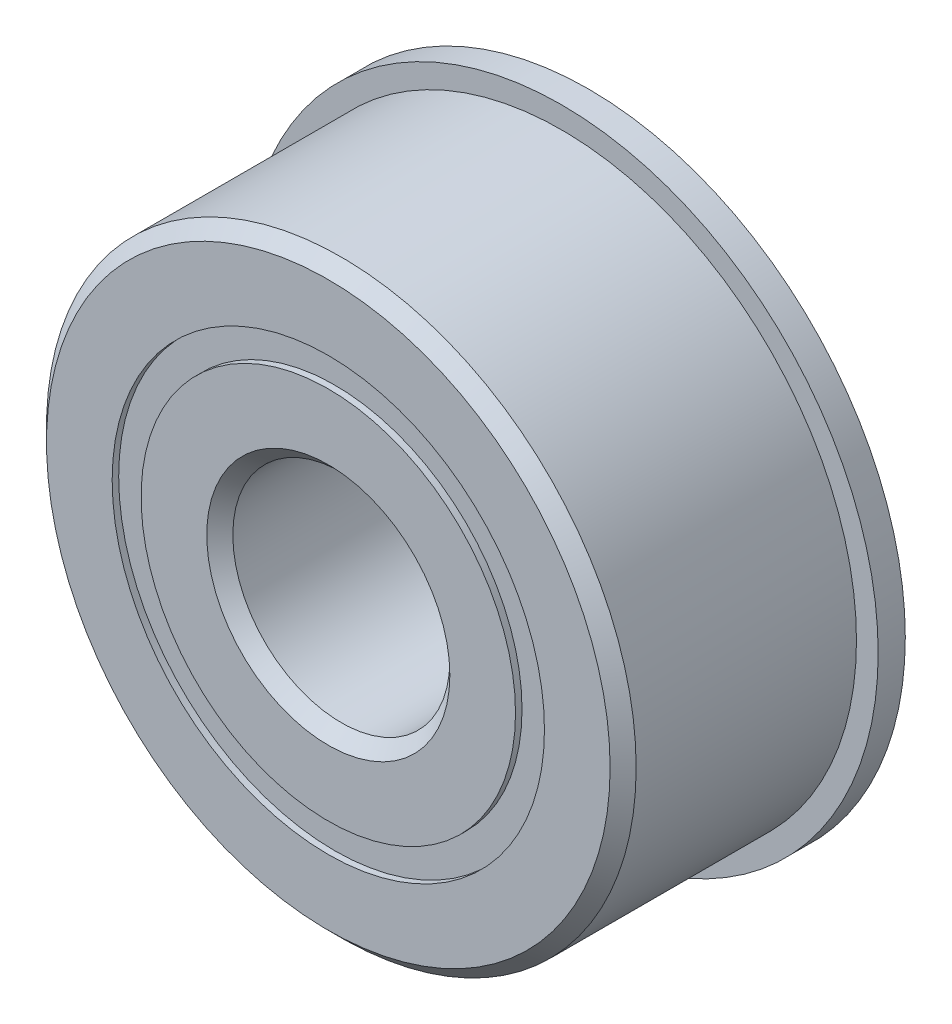
SolidWorks part; units mm, degrees
ref_plane "Front Plane" through (0, 0, 0) normal (0, 0, 1) x (1, 0, 0)
ref_plane "Top Plane" through (0, 0, 0) normal (0, 1, 0) x (1, 0, 0)
ref_plane "Right Plane" through (0, 0, 0) normal (1, 0, 0) x (0, 0, -1)
sketch "Sketch1" plane through (0, 0, 0) normal (1, 0, 0) x (0, 0, -1)
  line L0 (-3.6, 0) -> (3.6, 0) construction
  line L1 (0, 8.15) -> (0, -8.15) construction
  line L2 (3.24, 8.15) -> (-3.24, 8.15)
  line L3 (-3.24, 8.15) -> (-3.6, 7.79)
  line L4 (-3.6, 7.79) -> (-3.6, 5.975)
  line L5 (-3.6, 5.975) -> (-1.6, 5.975)
  line L6 (3.6, 5.975) -> (1.6, 5.975)
  line L7 (3.6, 7.79) -> (3.6, 5.975)
  line L8 (3.24, 8.15) -> (3.6, 7.79)
  line L9 (0, 8.15) -> (0, 5.575) construction
  line L10 (0, 5.575) -> (0, 3) construction
  arc A0 (-1.6, 5.975) -> (1.6, 5.975) centre (0, 5.575) cw
  point P14 (0, 3)
  dimension "Width" = 7.2
  dimension "OD" = 16.3
  dimension "D1" = 45
  dimension "D2" = 0.36
  dimension "Shaft Dia" = 6
  dimension "D3" = 3.2
  dimension "D4" = 0.4
revolve "Revolve1" add sketch "Sketch1" angle 360 about L0
sketch "Sketch3" plane through (0, 0, 0) normal (1, 0, 0) x (0, 0, -1)
  line L0 (-3.6, 5.175) -> (-1.6, 5.175)
  line L1 (0, 8.15) -> (0, -8.15) construction
  line L2 (-3.6, 7.79) -> (-3.6, 5.975) construction
  line L3 (-3.6, 5.175) -> (-3.6, 3.36)
  line L4 (-3.24, 8.15) -> (-3.6, 7.79) construction
  line L5 (-3.6, 3.36) -> (-3.24, 3)
  line L6 (-3.24, 3) -> (3.24, 3)
  line L7 (3.24, 8.15) -> (3.24, -8.15) construction
  line L8 (3.24, 3) -> (3.6, 3.36)
  line L9 (3.6, -7.79) -> (3.6, 7.79) construction
  line L10 (3.6, 3.36) -> (3.6, 5.175)
  line L11 (3.6, 5.175) -> (1.6, 5.175)
  line L13 (3.24, 8.15) -> (3.6, 7.79) construction
  arc A0 (1.6, 5.975) -> (-1.6, 5.975) centre (0, 5.575) ccw construction
  arc A1 (1.6, 5.175) -> (-1.6, 5.175) centre (0, 5.575) cw
revolve "Revolve3" add sketch "Sketch3" angle 360 about L0
sketch "Sketch4" plane through (0, 0, 0) normal (1, 0, 0) x (0, 0, -1)
  line L0 (-1.6492, 5.575) -> (1.6492, 5.575)
  arc A2 (-1.6492, 5.575) -> (1.6492, 5.575) centre (0, 5.575) cw
  arc A3 (1.6, 5.975) -> (-1.6, 5.975) centre (0, 5.575) ccw construction
revolve "Revolve4" add sketch "Sketch4" angle 360 about L0
ref_axis "Axis1" through (0, 0, -3.6) along (0, 0, 1)
pattern_circular "CirPattern1" count 8 every 45 about axis through (0, 0, -3.6) along (0, 0, 1) of bodies 104
sketch "Sketch5" plane through (0, 0, 0) normal (1, 0, 0) x (0, 0, -1)
  line L0 (-3.6, 5.975) -> (-1.6, 5.975) construction
  line L1 (-3.42, 5.975) -> (-1.6492, 5.975)
  line L2 (-3.42, 5.975) -> (-3.42, 5.175)
  line L3 (-3.42, 5.175) -> (-1.6492, 5.175)
  line L4 (-1.6492, 5.975) -> (-1.6492, 5.175)
  line L5 (-3.6, 5.175) -> (-1.6, 5.175) construction
  line L6 (3.6, 5.975) -> (1.6, 5.975) construction
  line L7 (3.42, 5.975) -> (1.6492, 5.975)
  line L8 (3.42, 5.975) -> (3.42, 5.175)
  line L9 (3.42, 5.175) -> (1.6492, 5.175)
  line L10 (1.6492, 5.975) -> (1.6492, 5.175)
  line L11 (3.6, 5.175) -> (1.6, 5.175) construction
  line L12 (-3.24, 8.15) -> (-3.6, 7.79) construction
  point P18 (-3.42, 7.97)
revolve "Revolve5" add sketch "Sketch5" angle 360 about L0
sketch "Sketch6" plane through (0, 0, 0) normal (1, 0, 0) x (0, 0, -1)
  line L0 (3.6, 0) -> (-3.6, 0) construction
  line L1 (3.6, 5.975) -> (2.85, 5.975)
  line L2 (3.6, 5.975) -> (3.6, 8.75)
  line L3 (3.6, 8.75) -> (2.85, 8.75)
  line L4 (2.85, 5.975) -> (2.85, 8.75)
  dimension "Th" = 0.75
  dimension "Flange OD" = 17.5
revolve "Revolve6" add sketch "Sketch6" angle 360 about L0
equation "\"D2@Sketch1\" = \"Width@Sketch1\"*.05"
equation "\"D3@Sketch1\" = \"Width@Sketch1\"/2.25"
equation "\"D4@Sketch1\" = (((\"OD@Sketch1\"-\"Width@Sketch1\")/2)/3.25)/3.5"
equation "\"D2@CirPattern1\" = 360/\"Balls@CirPattern1\""
